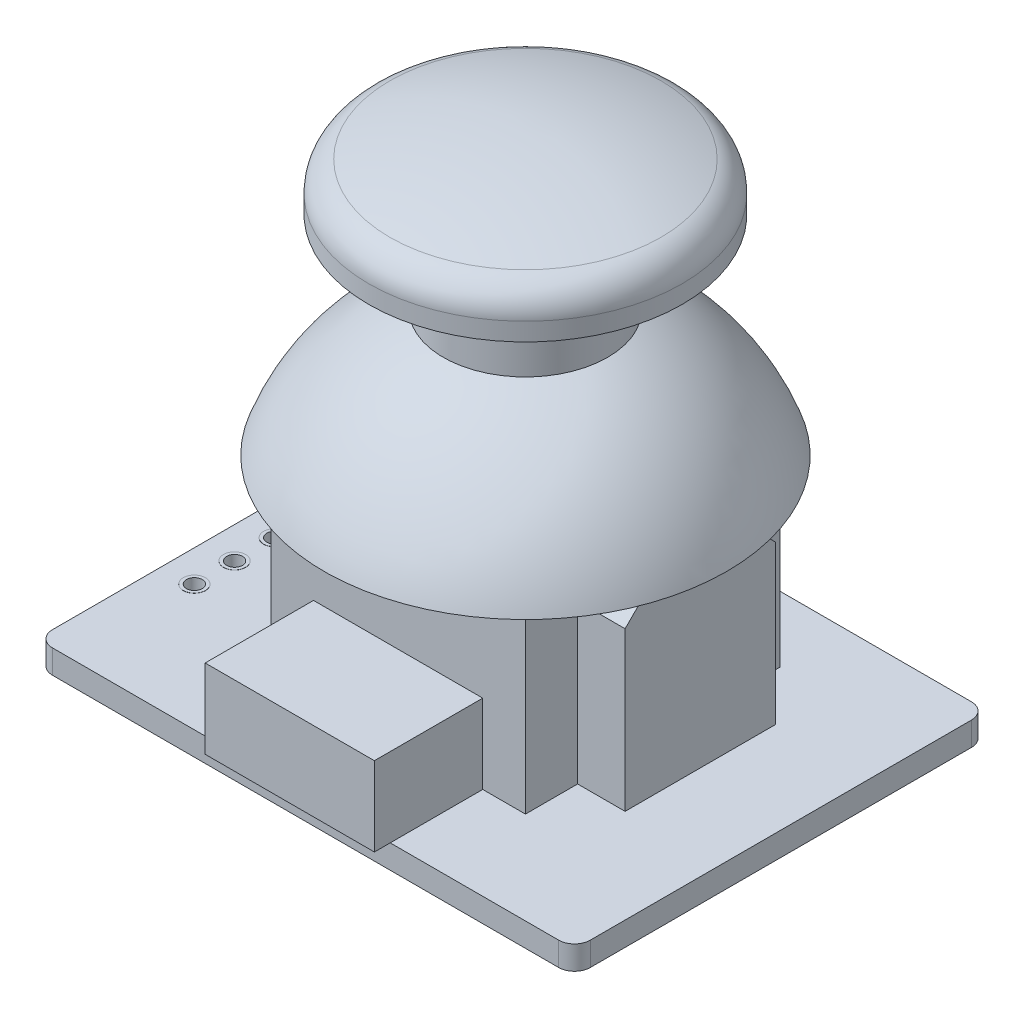
SolidWorks part; units mm, degrees
ref_plane "Front Plane" through (0, 0, 0) normal (0, 0, 1) x (1, 0, 0)
ref_plane "Top Plane" through (0, 0, 0) normal (0, 1, 0) x (1, 0, 0)
ref_plane "Right Plane" through (0, 0, 0) normal (1, 0, 0) x (0, 0, -1)
sketch "Sketch1" plane through (0, 0, 0) normal (0, 1, 0) x (1, 0, 0)
  line L1 (-17, 13.05) -> (17, 13.05)
  line L2 (-17, 13.05) -> (-17, -13.05)
  line L3 (-17, -13.05) -> (17, -13.05)
  line L4 (17, 13.05) -> (17, -13.05)
  line L5 (0, -13.05) -> (0, 13.05) construction
  line L6 (-17, 0) -> (17, 0) construction
  point P0 (0, 0)
  dimension "D1" = 26.1
  dimension "D2" = 34
extrude "PCB ext" add sketch "Sketch1" along normal blind 1.5
fillet "Fillet1" radius 1 4 edges at (-17, 0.75, 13.05) (-17, 0.75, -13.05) (17, 0.75, -13.05) (17, 0.75, 13.05)
sketch "Sketch14" plane through (0, 1.5, 0) normal (0, 1, 0) x (1, 0, 0)
  line L0 (-17, 0) -> (17, 0) construction
  line L1 (-17, 13.05) -> (-17, -13.05) construction
  circle A0 centre (-15, 0) radius 0.5
  dimension "D1" = 1
  dimension "D2" = 2
extrude "Cut-Extrude1" cut sketch "Sketch14" against normal through all
sketch "Sketch15" plane through (0, 1.5, 0) normal (0, 1, 0) x (1, 0, 0)
  circle A0 centre (-15, 0) radius 0.7
  circle A1 centre (-15, 0) radius 0.5 construction
  circle A3 centre (-15, 0) radius 0.5
  circle A4 centre (-15, 0) radius 0.5
  dimension "D1" = 0.2
  dimension "D2" = 0
extrude "Boss-Extrude6" add sketch "Sketch15" along normal blind 0.01
ref_plane "Plane2" through (0, 0.75, 0) normal (0, 1, 0) x (1, 0, 0)
mirror "Mirror1" about plane through (0, 0.75, 0) normal (0, 1, 0) of "Boss-Extrude6"
pattern_linear "LPattern1" count 3 spacing 2.54 along (0, 0, 1) count 3 spacing 2.54 along (0, 0, -1) of "Cut-Extrude1", "Boss-Extrude6", "Mirror1" pattern seed only yes
sketch "Sketch2" plane through (0, 1.5, 0) normal (0, 1, 0) x (1, 0, 0)
  line L0 (0, -13.05) -> (0, 13.05) construction
  line L1 (-8.05, 8.9) -> (8.05, 8.9)
  line L2 (-8.05, 8.9) -> (-8.05, -7.2)
  line L3 (-8.05, -7.2) -> (8.05, -7.2)
  line L4 (8.05, 8.9) -> (8.05, -7.2)
  line L5 (-17, -13.05) -> (17, -13.05) construction
  line L6 (-17, 13.05) -> (17, 13.05) construction
  line L10 (-8.05, -7.2) -> (8.05, 8.9) construction
  point P0 (0, 0.85)
  point P4 (0, 0.85)
  point P9 (0, 8.9)
  dimension "D1" = 13.9
  dimension "D2" = 12.2
  dimension "D3" = 16.1
extrude "Hat box" add sketch "Sketch2" along normal blind 12 separate body
ref_plane "Hat mox mid pln" through (0, 0, -0.85) normal (0, 0, 1) x (1, 0, 0)
sketch "Sketch10" plane through (0, 1.5, 0) normal (0, 1, 0) x (1, 0, 0)
  line L1 (8.05, -3.9) -> (11.05, -3.9)
  line L2 (8.05, -3.9) -> (8.05, 5.6)
  line L3 (8.05, 5.6) -> (11.05, 5.6)
  line L4 (11.05, -3.9) -> (11.05, 5.6)
  line L5 (8.05, 8.9) -> (8.05, -7.2) construction
  point P7 (8.05, 0.85)
  point P10 (8.05, 0.85)
  dimension "D1" = 3
  dimension "D2" = 9.5
extrude "Boss-Extrude5" add sketch "Sketch10" along normal up to surface (12 mm away) separate body up to face at (0, 13.5, -0.85)
chamfer "Chamfer1" distance 2 angle 45 2 edges at (9.55, 13.5, -5.6) (9.55, 13.5, 3.9)
sketch "Sketch12" plane through (0, 0, -0.85) normal (0, 0, 1) x (1, 0, 0)
  line L0 (0, -998.5) -> (0, 49001.5) construction
pattern_circular "CirPattern1" count 2 every 90 about axis through (0, -998.5, -0.85) along (0, 1, 0) of bodies 108
sketch "Sketch3" plane through (0, 1.5, 0) normal (0, 1, 0) x (1, 0, 0)
  line L1 (-5.35, -7.2) -> (5.35, -7.2)
  line L2 (-5.35, -7.2) -> (-5.35, -14.05)
  line L3 (-5.35, -14.05) -> (5.35, -14.05)
  line L4 (5.35, -7.2) -> (5.35, -14.05)
  line L7 (-8.05, -7.2) -> (8.05, -7.2) construction
  line L8 (-17, -13.05) -> (17, -13.05) construction
  point P6 (0, -7.2)
  point P7 (0, -7.2)
  point P8 (8.85, -14.9431)
  dimension "D1" = 10.7
  dimension "D2" = 1
extrude "Hat push button" add sketch "Sketch3" along normal blind 5
sketch "Sketch4" plane through (0, 13.5, 0) normal (0, 1, 0) x (1, 0, 0)
  circle A0 centre (0, 0.85) radius 2
  point P2 (3, -3.95)
  dimension "D1" = 4
extrude "Boss-Extrude4" add sketch "Sketch4" along normal blind 7.5
sketch "Sketch9" plane through (0, 0, -0.85) normal (0, 0, 1) x (1, 0, 0)
  line L0 (0, 20.7326) -> (0, 30.8)
  line L1 (-9.9, 30.8) -> (9.9, 30.8) construction
  line L4 (-997.6311, 8.6) -> (49002.3689, 8.6) construction
  line L6 (5.2, 26.3) -> (5.2, 21.0583)
  line L7 (5.2, 26.3) -> (9.9, 26.3)
  line L8 (9.9, 26.3) -> (9.9, 28.8)
  line L9 (-1021.7489, 13.1) -> (48978.2511, 13.1) construction
  line L10 (12.4093, 13.1) -> (12.7279, 13.1)
  line L11 (5.2, 20.7326) -> (0, 20.7326)
  line L13 (0, -961.886) -> (0, 49038.114) construction
  line L14 (0, 20.7326) -> (-5.2, 20.7326) construction
  line L16 (-16, 0) -> (16, 0) construction
  circle A0 centre (0, 8.6) radius 13.5 construction
  arc A3 (5.2, 21.0583) -> (12.7279, 13.1) centre (0, 8.6) cw
  arc A4 (0, 30.8) -> (9.9, 28.8) centre (0, 5.2975) cw
  arc A5 (5.2, 20.7326) -> (12.4093, 13.1) centre (0, 8.6) cw
  point P19 (0, 30.8)
  point P24 (0, 0)
  point P27 (0, 0)
  dimension "D1" = 27
  dimension "D5" = 2.5
  dimension "D3" = 4.5
  dimension "D9" = 0.3
  dimension "D4" = 10.4
  dimension "D7" = 19.8
  dimension "D8" = 4.5
  dimension "D6" = 30.8
  dimension "D2" = 8.6
revolve "Revolve1" add sketch "Sketch9" angle 360 about L13
fillet "Fillet2" radius 2 1 edges at (0, 28.8, -10.75)
equation "\"D1@Sketch9\"=13.5 * 2"
